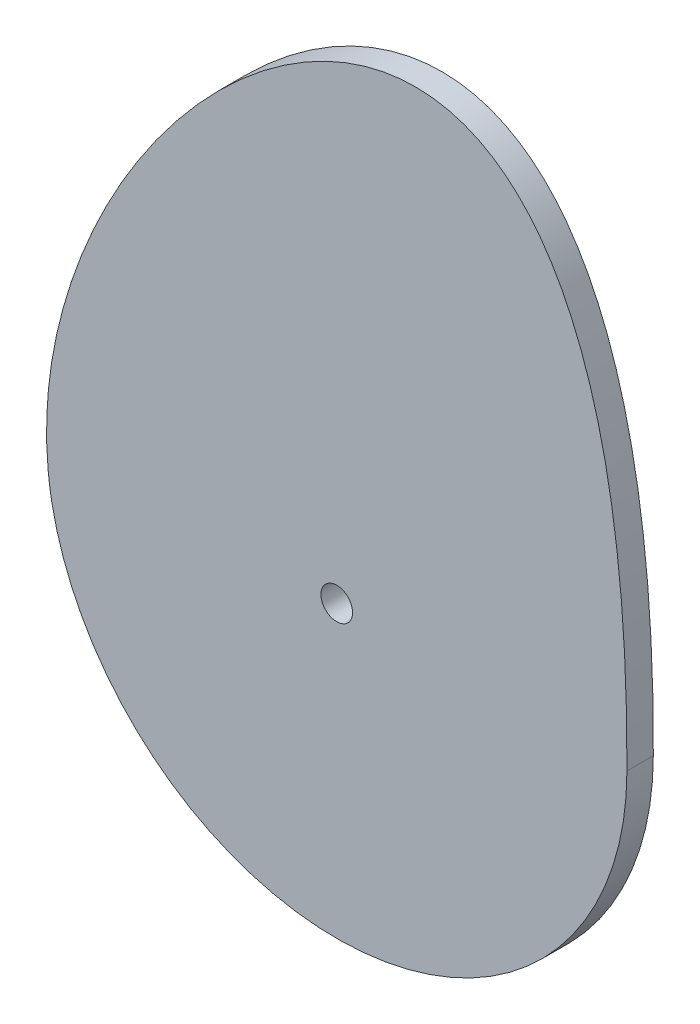
SolidWorks part; units mm, degrees
ref_plane "Front Plane" through (0, 0, 0) normal (0, 0, 1) x (1, 0, 0)
ref_plane "Top Plane" through (0, 0, 0) normal (0, 1, 0) x (1, 0, 0)
ref_plane "Right Plane" through (0, 0, 0) normal (1, 0, 0) x (0, 0, -1)
sketch "Sketch1" plane through (0, 0, 0) normal (0, 0, 1) x (1, 0, 0)
  circle A0 centre (0, 0) radius 55
  circle A1 centre (0, 0) radius 3
  spline S0 degree 3 poles (55, 0) (55.8439, 174.4246) (-67.02, 60.8439) (-54.0443, -10.2084) knots 0 0 0 0 1 1 1 1
  point P7 (-7.165, 154.3894)
  point P9 (-4.7659, 164.745)
  point P10 (-4.0109, 95.5172)
  point P11 (0, 72.989)
  point P12 (0, 88.9141)
  dimension "D1" = 6
  dimension "D2" = 110
extrude "Boss-Extrude1" add sketch "Sketch1" along normal blind 5 contours A0 S0 | A0 S0 region at (-53.1892, -4.9816, 0) region at (10.6678, 62.5729, 0)
